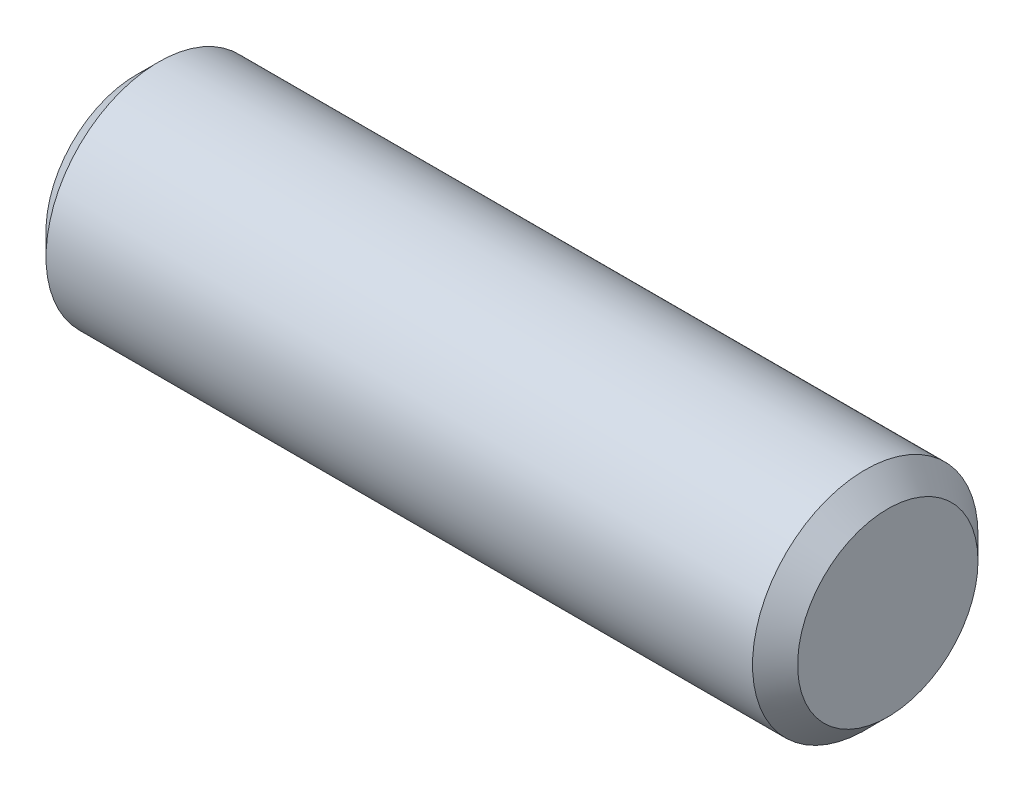
SolidWorks part; units mm, degrees
material "Delrin 2700 NC010, Low Viscosity Acetal Copolymer (SS)"
ref_plane "Front" through (0, 0, 0) normal (0, 0, 1) x (1, 0, 0)
ref_plane "Top" through (0, 0, 0) normal (0, 1, 0) x (1, 0, 0)
ref_plane "Right" through (0, 0, 0) normal (1, 0, 0) x (0, 0, -1)
sketch "Sketch1" plane through (0, 0, 0) normal (0, 0, 1) x (1, 0, 0)
  line L0 (-7.9375, 0) -> (7.9375, 0) construction
  line L1 (7.9375, 2.3813) -> (7.9375, -2.3813) construction
  line L2 (-7.9375, 2.3813) -> (-7.9375, -2.3813) construction
  dimension "Length" = 15.875
  dimension "Diameter" = 4.7625
sketch "Sketch2" plane through (0, 0, 0) normal (1, 0, 0) x (0, 0, -1)
  circle A0 centre (0, 0) radius 2.3813
extrude "Extrude1" add sketch "Sketch2" against normal up to vertex (7.9375 mm away) and the other way up to vertex (7.9375 mm away) up to point (-7.9375, 2.3813, 0) other way up to point (7.9375, 2.3813, 0)
chamfer "Chamfer1" distance 0.4763 angle 45 2 edges at (7.9375, 0, -2.3813) (-7.9375, 0, -2.3813)
equation "\"D1@Chamfer1\" = \"Diameter@Sketch1\"*.1"
